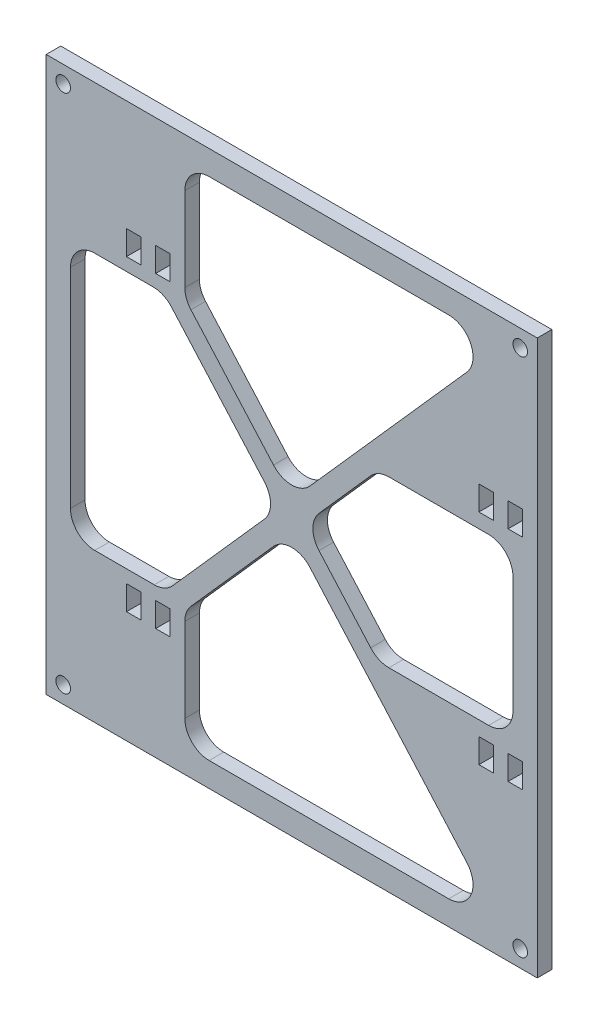
SolidWorks part; units mm, degrees
ref_plane "Front Plane" through (0, 0, 0) normal (0, 0, 1) x (1, 0, 0)
ref_plane "Top Plane" through (0, 0, 0) normal (0, 1, 0) x (1, 0, 0)
ref_plane "Right Plane" through (0, 0, 0) normal (1, 0, 0) x (0, 0, -1)
sketch "Sketch1" plane through (0, 0, 0) normal (0, 0, 1) x (1, 0, 0)
  line L0 (71.6864, -54.1061) -> (71.6572, -54.0732)
  line L1 (71.6864, 56.8779) -> (-29.3136, 56.8779)
  line L2 (71.6864, 56.8779) -> (71.6864, -57.1221)
  line L3 (71.6864, -57.1221) -> (-29.3136, -57.1221)
  line L4 (-29.3136, 56.8779) -> (-29.3136, -57.1221)
  line L5 (71.6864, 56.8779) -> (-29.3136, -57.1221) construction
  line L6 (71.6864, -57.1221) -> (-29.3136, 56.8779) construction
  line L7 (-11.1018, -52.1221) -> (53.4747, -52.1221)
  line L8 (-24.3136, -35.2791) -> (-24.3136, 35.035)
  line L9 (-11.1018, 51.8779) -> (53.4747, 51.8779)
  line L10 (66.6864, -35.2791) -> (66.6864, 35.035)
  line L11 (-23.7247, -50.8138) -> (66.0975, 50.5697) construction
  line L12 (-23.7247, 50.5697) -> (66.0975, -50.8138) construction
  line L13 (69.0144, 56.8779) -> (68.9414, 56.7956)
  line L14 (69.0144, -57.1221) -> (68.9414, -57.0397)
  line L15 (71.6864, 53.862) -> (71.6572, 53.829)
  line L16 (73.1834, 55.5517) -> (-27.8166, -58.4483) construction
  line L17 (70.1894, 58.2042) -> (-30.8106, -55.7958) construction
  line L18 (57.9439, 38.3507) -> (26.796, 3.1936)
  line L19 (57.2172, 43.5622) -> (24.9289, 7.1181)
  line L20 (17.4439, -7.3622) -> (-14.8443, -43.8064)
  line L21 (17.4439, 7.1181) -> (-14.8443, 43.5622)
  line L22 (73.1834, -55.7958) -> (-27.8166, 58.2042) construction
  line L23 (15.5768, -3.4378) -> (-15.5711, -38.5948)
  line L24 (15.5768, 3.1936) -> (-15.5711, 38.3507)
  line L25 (70.1894, -58.4483) -> (-30.8106, 55.5517) construction
  line L26 (57.9439, -38.5948) -> (26.796, -3.4378)
  line L27 (57.2172, -43.8064) -> (24.9289, -7.3622)
  line L28 (-26.5685, -57.0397) -> (-26.6415, -57.1221)
  line L29 (-29.2844, -54.0732) -> (-29.3136, -54.1061)
  circle A0 centre (68.1864, 53.3779) radius 1.5
  circle A1 centre (68.1864, -53.6221) radius 1.5
  circle A2 centre (-25.8136, -53.6221) radius 1.5
  circle A3 centre (-25.8136, 53.3779) radius 1.5
  circle A4 centre (-25.8136, 53.3779) radius 3.5 construction
  circle A5 centre (-25.8136, -53.6221) radius 3.5 construction
  circle A6 centre (68.1864, -53.6221) radius 3.5 construction
  circle A7 centre (68.1864, 53.3779) radius 3.5 construction
  arc A9 (15.5768, 3.1936) -> (15.5768, -3.4378) centre (11.8343, -0.1221) cw
  arc A10 (17.4439, -7.3622) -> (24.9289, -7.3622) centre (21.1864, -10.6779) cw
  arc A11 (26.796, -3.4378) -> (26.796, 3.1936) centre (30.5385, -0.1221) cw
  arc A12 (24.9289, 7.1181) -> (17.4439, 7.1181) centre (21.1864, 10.4338) cw
  arc A13 (-11.1018, 51.8779) -> (-14.8443, 43.5622) centre (-11.1018, 46.8779) ccw
  arc A14 (-15.5711, 38.3507) -> (-24.3136, 35.035) centre (-19.3136, 35.035) ccw
  arc A15 (-15.5711, -38.5948) -> (-24.3136, -35.2791) centre (-19.3136, -35.2791) cw
  arc A16 (-14.8443, -43.8064) -> (-11.1018, -52.1221) centre (-11.1018, -47.1221) ccw
  arc A17 (57.2172, -43.8064) -> (53.4747, -52.1221) centre (53.4747, -47.1221) cw
  arc A18 (66.6864, -35.2791) -> (57.9439, -38.5948) centre (61.6864, -35.2791) cw
  arc A19 (66.6864, 35.035) -> (57.9439, 38.3507) centre (61.6864, 35.035) ccw
  arc A20 (57.2172, 43.5622) -> (53.4747, 51.8779) centre (53.4747, 46.8779) ccw
  point P0 (21.1864, -0.1221)
  point P6 (21.1864, -0.1221)
  point P67 (18.5144, -0.1221)
  point P84 (64.5846, -52.1221)
  point P87 (66.6864, -48.4625)
  dimension "D4" = 5
  dimension "D1" = 2
  dimension "D2" = 2
  dimension "D3" = 2
extrude "Boss-Extrude1" add sketch "Sketch1" along normal blind 3 contours L1 L4 L3 L2 A20 L19 A12 L21 A13 L9 A19 L10 A18 L26 A11 L18 L23 A15 L8 A14 L24 A9 A3 A2 A1 A0 region at (21.1864, -0.1221, 0)
sketch "Sketch2" plane through (0, 0, 3) normal (0, 0, 1) x (1, 0, 0)
  line L0 (66.6864, -35.2791) -> (66.6864, 35.035) construction
  line L1 (65.6864, 24.8779) -> (68.6864, 24.8779)
  line L2 (65.6864, 24.8779) -> (65.6864, 19.8779)
  line L3 (65.6864, 19.8779) -> (68.6864, 19.8779)
  line L4 (68.6864, 24.8779) -> (68.6864, 19.8779)
  line L5 (69.5256, 16.8779) -> (38.9199, 16.8779)
  line L6 (57.9439, 38.3507) -> (26.796, 3.1936) construction
  line L7 (69.5392, -17.1221) -> (38.9199, -17.1221)
  line L8 (57.9439, -38.5948) -> (26.796, -3.4378) construction
  line L9 (71.6864, 56.8779) -> (71.6864, -57.1221) construction
  line L10 (59.6864, 24.8779) -> (62.6864, 24.8779)
  line L11 (59.6864, 24.8779) -> (59.6864, 19.8779)
  line L12 (62.6864, 24.8779) -> (62.6864, 19.8779)
  line L13 (59.6864, 19.8779) -> (62.6864, 19.8779)
  line L14 (65.6864, -20.1221) -> (68.6864, -20.1221)
  line L15 (65.6864, -20.1221) -> (65.6864, -25.1221)
  line L16 (65.6864, -25.1221) -> (68.6864, -25.1221)
  line L17 (68.6864, -20.1221) -> (68.6864, -25.1221)
  line L18 (59.6864, -20.1221) -> (62.6864, -20.1221)
  line L19 (59.6864, -20.1221) -> (59.6864, -25.1221)
  line L20 (62.6864, -20.1221) -> (62.6864, -25.1221)
  line L21 (59.6864, -25.1221) -> (62.6864, -25.1221)
  line L22 (61.1864, 19.8779) -> (61.1864, -20.1221) construction
  line L23 (66.6864, -0.1221) -> (61.1864, -0.1221) construction
  line L24 (38.9199, -17.1221) -> (69.5392, -51.6825)
  line L25 (69.5392, -51.6825) -> (69.5392, -17.1221)
  line L26 (38.9199, 16.8779) -> (69.5256, 52.2365)
  line L27 (69.5256, 52.2365) -> (69.5256, 16.8779)
  arc A0 (57.9439, -38.5948) -> (66.6864, -35.2791) centre (61.6864, -35.2791) ccw construction
  arc M27 (57.9439, 38.3507) -> (66.6864, 35.035) centre (61.6864, 35.035) cw
  line M28 (66.6864, 35.035) -> (66.6864, -35.2791)
  dimension "D1" = 3
  dimension "D2" = 5
  dimension "D3" = 3
  dimension "D6" = 40
  dimension "D7" = 3
  dimension "D8" = 3
  dimension "D9" = 3
  dimension "D4" = 2
  dimension "D5" = 2
extrude "Boss-Extrude2" add sketch "Sketch2" against normal blind 3
extrude "Cut-Extrude1" cut sketch "Sketch2<2>" against normal blind 3 contours L4 L1 L3 M27 M28 | L17 L16 L15 L14 region at (67.6864, 22.3779, 3)
sketch "Sketch2<2>" plane through (0, 0, 3) normal (0, 0, 1) x (1, 0, 0) same geometry as "Sketch2"
sketch "Sketch3" plane through (0, 0, 3) normal (0, 0, 1) x (1, 0, 0)
  line L0 (-12.7945, -29.1221) -> (-9.7945, -29.1221)
  line L1 (17.4439, -7.3622) -> (-14.8443, -43.8064) construction
  line L2 (-12.7945, -29.1221) -> (-12.7945, -34.1221) construction
  line L3 (-12.7945, -34.1221) -> (-15.7945, -34.1221) construction
  line L9 (-12.7945, -29.1221) -> (-12.7945, -34.1221)
  line L10 (-12.7945, -34.1221) -> (-9.7945, -34.1221)
  line L11 (-9.7945, -29.1221) -> (-9.7945, -34.1221)
  line L12 (-6.7945, -29.1221) -> (-3.7945, -29.1221)
  line L13 (-6.7945, -29.1221) -> (-6.7945, -34.1221)
  line L14 (-6.7945, -34.1221) -> (-3.7945, -34.1221)
  line L15 (-3.7945, -29.1221) -> (-3.7945, -34.1221)
  line L18 (-0.7945, -27.9482) -> (-0.7945, -52.1221)
  line L20 (-11.1018, -52.1221) -> (53.4747, -52.1221) construction
  line L21 (-0.7945, -26.468) -> (-24.3136, -26.468)
  line L24 (-0.7945, -27.9482) -> (-0.7945, -26.468)
  line L25 (-24.3136, -26.468) -> (-24.3136, -52.1221)
  line L26 (-24.3136, -52.1221) -> (-0.7945, -52.1221)
  dimension "D2" = 3
  dimension "D3" = 5
  dimension "D6" = 3
  dimension "D4" = 3
extrude "Boss-Extrude3" add sketch "Sketch3" against normal blind 3
extrude "Cut-Extrude2" cut sketch "Sketch3<2>" against normal blind 3 contours L11 L10 L9 L0 | L13 L14 L15 L12
sketch "Sketch3<2>" plane through (0, 0, 3) normal (0, 0, 1) x (1, 0, 0) same geometry as "Sketch3"
mirror "Mirror1" about plane through (0, 0, 0) normal (0, 1, 0) of "Boss-Extrude3", "Cut-Extrude2"
fillet "Fillet4" radius 5 12 edges at (-4.8272, -26.468, 1.5) (-24.3136, -26.468, 1.5) (-0.7945, -52.1221, 1.5) (-0.7945, -27.9482, 1.5) (-0.7945, 51.8779, 1.5) (-0.7945, 27.704, 1.5) (-24.3136, 26.468, 1.5) (-5.0435, 26.468, 1.5) (38.9199, 16.8779, 1.5) (66.6864, 16.8779, 1.5) (66.6864, -17.1221, 1.5) (38.9199, -17.1221, 1.5)
